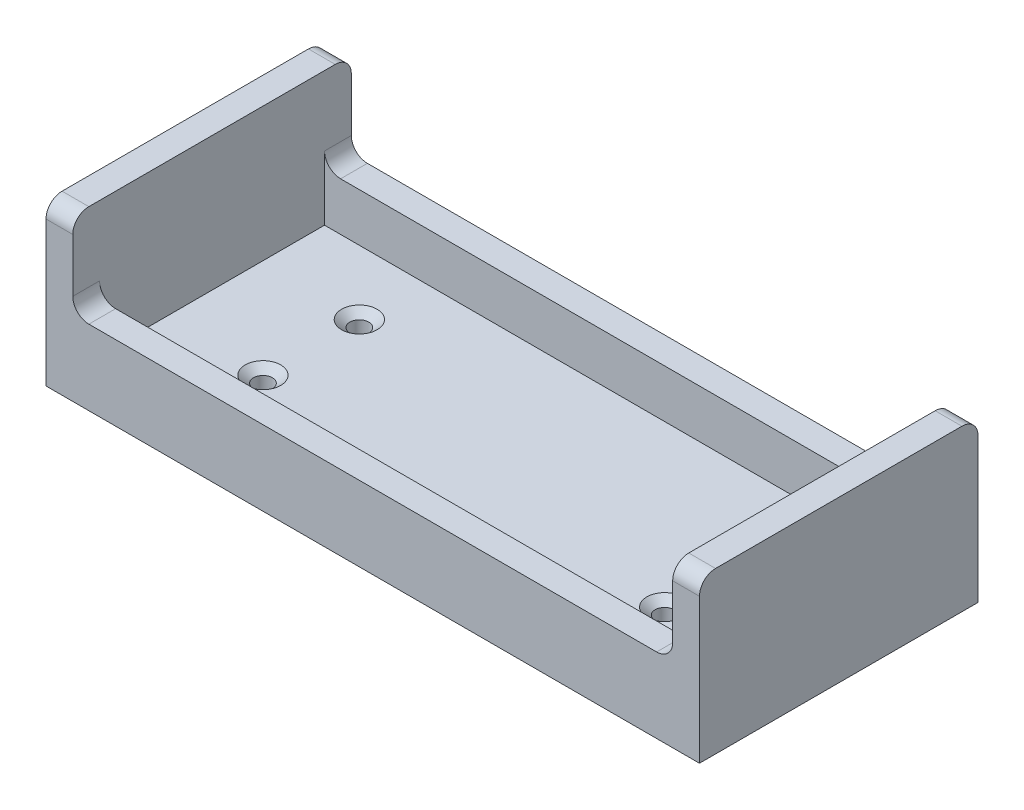
SolidWorks part; units mm, degrees
material "PET"
ref_plane "Front Plane" through (0, 0, 0) normal (0, 0, 1) x (1, 0, 0)
ref_plane "Top Plane" through (0, 0, 0) normal (0, 1, 0) x (1, 0, 0)
ref_plane "Right Plane" through (0, 0, 0) normal (1, 0, 0) x (0, 0, -1)
sketch "Sketch1" plane through (0, 0, 0) normal (0, 1, 0) x (1, 0, 0)
  line L0 (-69.4555, 22.0678) -> (-69.4555, 28.4178)
  line L5 (-69.4555, 22.0678) -> (72.7845, 22.0678)
  line L6 (-69.4555, 22.0678) -> (-69.4555, -31.2722)
  line L7 (-69.4555, -31.2722) -> (72.7845, -31.2722)
  line L8 (72.7845, 22.0678) -> (72.7845, -31.2722)
  line L9 (-75.8055, 28.4178) -> (79.1345, 28.4178)
  line L10 (-75.8055, 28.4178) -> (-75.8055, -37.6222)
  line L11 (-75.8055, -37.6222) -> (79.1345, -37.6222)
  line L12 (79.1345, 28.4178) -> (79.1345, -37.6222)
  line L13 (-69.4555, -31.2722) -> (-69.4555, -37.6222)
  line L14 (72.7845, 22.0678) -> (72.7845, 28.4178)
  line L15 (72.7845, -31.2722) -> (72.7845, -37.6222)
  point P0 (-49.1267, -9.4869)
  point P1 (-49.1267, 8.7015)
  point P2 (50.9319, 8.7015)
  point P3 (50.9319, -9.4869)
  point P8 (0, 0)
  dimension "D1" = 154.94
  dimension "D2" = 66.04
  dimension "D3" = 142.24
  dimension "D4" = 53.34
  dimension "D5" = 6.35
  dimension "D6" = 6.35
sketch "Sketch3" plane through (0, 0, 0) normal (0, 1, 0) x (1, 0, 0)
  line L1 (-69.4555, 22.0678) -> (72.7845, 22.0678)
  line L2 (-69.4555, 22.0678) -> (-69.4555, -31.2722)
  line L3 (-69.4555, -31.2722) -> (72.7845, -31.2722)
  line L4 (72.7845, 22.0678) -> (72.7845, -31.2722)
ref_plane "Plane2" through (72.39, 0, 0) normal (1, 0, 0) x (0, 0, -1)
extrude "Boss-Extrude1" add sketch "Sketch1" along normal blind 38.1 contours L8 L15 L11 L12 L9 L14 | L13 L6 L0 L9 L10 L11 region at (-72.6305, 0, 4.6022) region at (75.9595, 0, 4.6022)
extrude "Boss-Extrude2" add sketch "Sketch1<4>" along normal blind 6.35 contours L8 L5 L6 L7 region at (1.6645, 0, 4.6022)
sketch "Sketch1<4>" plane through (0, 0, 0) normal (0, 1, 0) x (1, 0, 0) same geometry as "Sketch1"
extrude "Boss-Extrude3" add sketch "Sketch1<5>" along normal blind 17.78 contours L5 L14 L9 L0 | L15 L7 L13 L11 region at (1.6645, 0, -25.2428) region at (1.6645, 0, 34.4472)
sketch "Sketch1<5>" plane through (0, 0, 0) normal (0, 1, 0) x (1, 0, 0) same geometry as "Sketch1"
fillet "Fillet1" radius 3.81 8 edges at (72.7845, 17.78, 34.4472) (72.7845, 17.78, -25.2428) (75.9595, 38.1, -28.4178) (75.9595, 38.1, 37.6222) (-72.6305, 38.1, -28.4178) (-69.4555, 17.78, -25.2428) (-69.4555, 17.78, 34.4472) (-72.6305, 38.1, 37.6222)
sketch "Sketch7" plane through (0, 6.35, 0) normal (0, 1, 0) x (1, 0, 0)
  line L2 (-75.8055, 24.6078) -> (-75.8055, -33.8122) construction
  line L5 (-65.6455, 28.4178) -> (68.9745, 28.4178) construction
  point P0 (-45.9605, 6.8278)
  point P1 (-45.9605, -16.0322)
  point P2 (49.2895, -16.0322)
  point P3 (49.2895, 6.8278)
  point P4 (0, 0)
  point P6 (-48.1473, -39.2866)
  dimension "D1" = 22.86
  dimension "D2" = 22.86
  dimension "D3" = 95.25
  dimension "D4" = 95.25
  dimension "D5" = 29.845
  dimension "D6" = 21.59
  dimension "D7" = 21.59
hole_wizard "CSK for #8 Flat Head Machine Screw (100)2" positions "Sketch8" profile "Sketch9" countersink size "#8" standard "ANSI Inch" end condition through all
sketch "Sketch8" plane through (0, 6.35, 0) normal (0, 1, 0) x (1, 0, 0)
  point P0 (-45.9605, -16.0322)
  point P3 (-45.9605, 6.8278)
  point P6 (49.2895, 6.8278)
  point P9 (49.2895, -16.0322)
sketch "Sketch9" plane through (-45.9605, 6.35, 16.0322) normal (1, 0, 0) x (0, 0, 1)
  line L0 (0, 0) -> (0, 6.35)
  line L1 (0, 6.35) -> (2.2479, 6.35)
  line L2 (2.2479, 6.35) -> (2.2479, 1.6518)
  line L3 (2.2479, 1.6518) -> (4.2164, 0)
  line L5 (4.2164, 0) -> (0, 0)
  line L6 (-2.2479, 1.6518) -> (-4.2164, 0) construction
  line L11 (0, -6.35) -> (0, 107.95) construction
  dimension "Thru Hole Dia." = 4.4958
  dimension "Thru Hole Depth" = 6.35
  dimension "Near C'Sink Dia." = 8.4328
  dimension "Near C'Sink Angle" = 100
